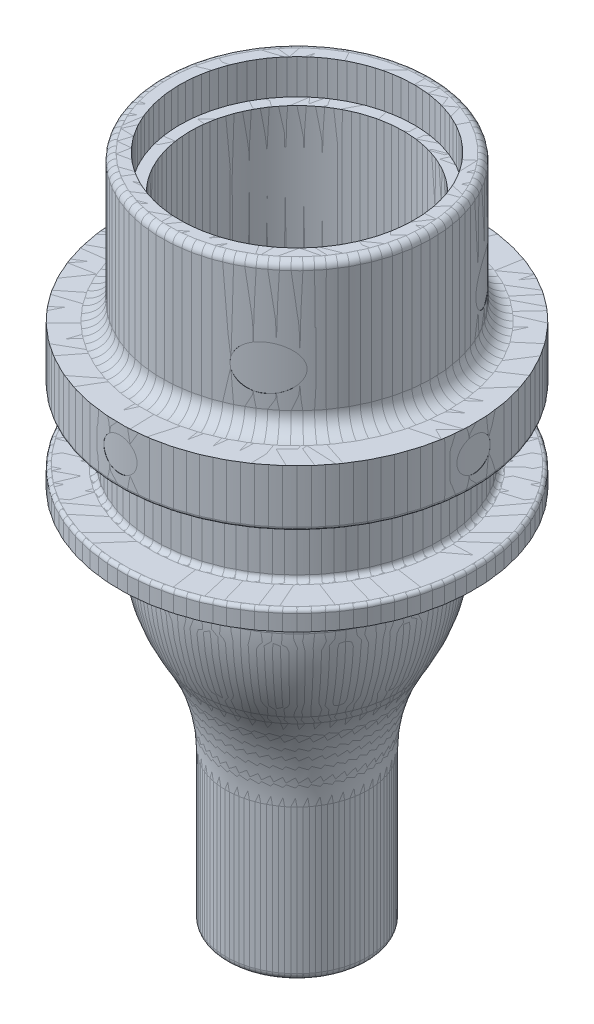
SolidWorks part; units mm, degrees
other "SwirlInner"
other "Spun Profile"
material "Brass"
ref_plane "Front Plane" through (0, 0, 0) normal (0, 0, 1) x (1, 0, 0)
ref_plane "Top Plane" through (0, 0, 0) normal (0, 1, 0) x (1, 0, 0)
ref_plane "Right Plane" through (0, 0, 0) normal (1, 0, 0) x (0, 0, -1)
sketch "Sketch1" plane through (0, 0, 0) normal (0, 0, 1) x (1, 0, 0)
  line L0 (4.826, 23.876) -> (4.826, 18.6563)
  line L2 (6.3373, 17.3228) -> (6.3373, 16.7513)
  line L3 (6.3373, 13.5128) -> (5.0673, 13.5128)
  line L5 (4.445, 10.4116) -> (2.54, 7.112)
  line L6 (2.54, 7.112) -> (2.54, 0)
  line L7 (2.54, 0) -> (2.032, 0)
  line L8 (2.032, 0) -> (2.032, 7.332)
  line L9 (2.032, 7.332) -> (3.81, 10.4116)
  line L10 (3.81, 10.4116) -> (3.81, 22.6314)
  line L11 (4.191, 23.876) -> (4.826, 23.876)
  line L12 (0, 20.955) -> (0, 0) construction
  line L13 (6.2103, 16.6243) -> (5.2578, 16.6243)
  line L14 (5.08, 16.4465) -> (5.08, 14.3891)
  line L15 (5.2578, 14.2113) -> (6.2103, 14.2113)
  line L16 (5.08, 13.5128) -> (5.08, 17.3228) construction
  line L17 (6.3373, 14.0843) -> (6.3373, 13.5128)
  line L18 (5.0673, 13.5128) -> (4.445, 13.5128)
  line L19 (4.445, 13.5128) -> (4.445, 10.4116)
  line L20 (6.3373, 17.3228) -> (6.3373, 18.6563)
  line L21 (6.3373, 18.6563) -> (4.826, 18.6563)
  line L22 (4.191, 23.876) -> (4.191, 22.6314)
  line L23 (4.191, 22.6314) -> (3.81, 22.6314)
  arc A0 (6.2103, 14.2113) -> (6.3373, 14.0843) centre (6.2103, 14.0843) cw
  arc A1 (6.2103, 16.6243) -> (6.3373, 16.7513) centre (6.2103, 16.7513) ccw
  arc A2 (5.08, 14.3891) -> (5.2578, 14.2113) centre (5.2578, 14.3891) ccw
  arc A3 (5.2578, 16.6243) -> (5.08, 16.4465) centre (5.2578, 16.4465) ccw
  point P20 (5.08, 15.4178)
  point P36 (6.3373, 14.2113)
  point P41 (5.08, 14.2113)
  point P44 (5.08, 16.6243)
  dimension "D14" = 0.127
  dimension "D15" = 0.1778
  dimension "D1" = 6.3373
  dimension "D3" = 0.6985
  dimension "D4" = 7.112
  dimension "D5" = 0.508
  dimension "D6" = 30
  dimension "D7" = 10.3632
  dimension "D8" = 2.54
  dimension "D9" = 1.27
  dimension "D10" = 2.413
  dimension "D11" = 5.08
  dimension "D12" = 0.635
  dimension "D13" = 150
  dimension "D16" = 20.955
  dimension "D17" = 1.016
  dimension "D18" = 3.81
  dimension "D19" = 2.032
  dimension "D20" = 1.2446
  dimension "D21" = 0.381
  dimension "D22" = 23.876
  dimension "D23" = 2.032
revolve "Revolve1" add sketch "Sketch1" angle 360 about L12
sketch "Sketch2" plane through (0, 0, 0) normal (0, 0, 1) x (1, 0, 0)
  line L0 (3.81, 23.876) -> (-3.81, 23.876) construction
  point P0 (2.794, 20.574)
  dimension "D1" = 3.302
  dimension "D2" = 2.794
hole_wizard "1/16 (0.0625) Diameter Hole1" positions "Sketch2" profile "Sketch3" hole size "1/16" standard "ANSI Inch" end condition through all
sketch "Sketch3" plane through (2.794, 20.574, 0) normal (1, 0, 0) x (0, 1, 0)
  line L0 (0, 0) -> (0, 6.3373)
  line L1 (0, 6.3373) -> (0.7937, 6.3373)
  line L2 (0.7937, 6.3373) -> (0.7937, 0)
  line L5 (0.7937, 0) -> (0, 0)
  line L11 (0, -6.35) -> (0, 107.95) construction
  dimension "Thru Hole Dia." = 1.5875
  dimension "Thru Hole Depth" = 6.3373
pattern_circular "CirPattern1" count 4 over 360 about axis through (0, 20.955, 0) along (0, 1, 0) of "1/16 (0.0625) Diameter Hole1" reverse direction yes
ref_plane "Plane1" through (0, 0, 6.3373) normal (0, 0, 1) x (1, 0, 0)
sketch "Sketch5" plane through (0, 0, 6.3373) normal (0, 0, 1) x (1, 0, 0)
  line L0 (0, 16.7513) -> (0, 18.6563) construction
  line L1 (6.3373, 18.6563) -> (-6.3373, 18.6563) construction
  line L2 (-6.3373, 16.7513) -> (6.3373, 16.7513) construction
  point P0 (0, 17.7038)
  point P8 (0, 17.7038)
hole_wizard "#0-80 Tapped Hole1" positions "Sketch5" profile "Sketch7" tap size "#0-80" standard "ANSI Inch"
sketch "Sketch7" plane through (0, 17.7038, 6.3373) normal (1, 0, 0) x (0, -1, 0)
  line L0 (0, 0) -> (0, 2.1359)
  line L1 (0, 2.1359) -> (0.5956, 1.778)
  line L2 (0.5956, 1.778) -> (0.5956, 0)
  line L5 (0.5956, 0) -> (0, 0)
  line L10 (0, 2.1359) -> (-0.5956, 1.778) construction
  line L11 (0, -6.35) -> (0, 107.95) construction
  dimension "Tap Drill Dia." = 1.1913
  dimension "Tap Drill Depth" = 1.778
  dimension "Drill Angle" = 118
cosmetic thread "Hole Thread2" parameters "D1"=1.778, "D2"=1.524
pattern_circular "CirPattern2" count 4 over 360 about axis through (0, 20.955, 0) along (0, 1, 0) of "#0-80 Tapped Hole1" reverse direction yes
cosmetic thread "Hole Thread3" parameters "D1"=1.778, "D2"=1.524
cosmetic thread "Hole Thread4" parameters "D1"=1.778, "D2"=1.524
cosmetic thread "Hole Thread5" parameters "D1"=1.778, "D2"=1.524
fillet "Fillet1" radius 0.254 1 edges at (-4.826, 23.876, 0)
fillet "Fillet2" radius 6.35 2 edges at (-3.81, 10.4116, 0) (-2.032, 7.332, 0)
fillet "Fillet3" radius 6.35 2 edges at (-4.445, 10.4116, 0) (-2.54, 7.112, 0)
fillet "Fillet4" radius 0.635 1 edges at (-4.826, 18.6563, 0)
fillet "Fillet5" radius 0.254 2 edges at (-2.032, 0, 0) (-2.54, 0, 0)
fillet "Fillet6" radius 0.762 1 edges at (-4.445, 13.5128, 0)
ref_plane "Plane2" through (0, 20.955, 0) normal (1, 0, 0) x (0, 1, 0)
sketch "Spun Profile Sketch2" plane through (0, 20.955, 0) normal (1, 0, 0) x (0, 1, 0)
  line L0 (-4.3307, 6.2103) -> (-4.3307, 5.2578)
  line L1 (-4.5085, 5.08) -> (-6.5659, 5.08)
  line L2 (-6.7437, 5.2578) -> (-6.7437, 6.2103)
  line L3 (-6.8707, 6.3373) -> (-7.4422, 6.3373)
  line L4 (-7.4422, 6.3373) -> (-7.4422, 5.207)
  line L5 (-8.2042, 4.445) -> (-8.842, 4.445)
  line L6 (-12.017, 3.5943) -> (-12.3695, 3.3907)
  line L7 (-15.5445, 2.54) -> (-20.701, 2.54)
  line L8 (-20.701, 2.032) -> (-15.3245, 2.032)
  line L9 (-12.1495, 2.8827) -> (-12.017, 2.9593)
  line L10 (-8.842, 3.81) -> (1.6764, 3.81)
  line L11 (1.6764, 3.81) -> (1.6764, 4.191)
  line L12 (1.6764, 4.191) -> (2.921, 4.191)
  line L13 (2.921, 4.191) -> (2.921, 4.572)
  line L14 (2.667, 4.826) -> (-1.6637, 4.826)
  line L15 (-2.2987, 5.461) -> (-2.2987, 6.3373)
  line L16 (-2.2987, 6.3373) -> (-4.2037, 6.3373)
  line L17 (0, 0) -> (1000, 0) construction
  arc A0 (-4.2037, 6.3373) -> (-4.3307, 6.2103) centre (-4.2037, 6.2103) ccw
  arc A1 (-4.3307, 5.2578) -> (-4.5085, 5.08) centre (-4.5085, 5.2578) cw
  arc A2 (-6.5659, 5.08) -> (-6.7437, 5.2578) centre (-6.5659, 5.2578) cw
  arc A3 (-6.7437, 6.2103) -> (-6.8707, 6.3373) centre (-6.8707, 6.2103) ccw
  arc A4 (-7.4422, 5.207) -> (-8.2042, 4.445) centre (-8.2042, 5.207) cw
  arc A5 (-8.842, 4.445) -> (-12.017, 3.5943) centre (-8.842, -1.905) ccw
  arc A6 (-12.3695, 3.3907) -> (-15.5445, 2.54) centre (-15.5445, 8.89) cw
  arc A7 (-20.701, 2.54) -> (-20.701, 2.032) centre (-20.701, 2.286) ccw
  arc A8 (-15.3245, 2.032) -> (-12.1495, 2.8827) centre (-15.3245, 8.382) ccw
  arc A9 (-12.017, 2.9593) -> (-8.842, 3.81) centre (-8.842, -2.54) cw
  arc A10 (2.921, 4.572) -> (2.667, 4.826) centre (2.667, 4.572) ccw
  arc A11 (-1.6637, 4.826) -> (-2.2987, 5.461) centre (-1.6637, 5.461) cw
revolve "Revolve" add sketch "Spun Profile Sketch2" angle 360 about L17
ref_plane "FrontFace" through (0, -0.254, 0) normal (0, -1, 0) x (-1, 0, 0)
